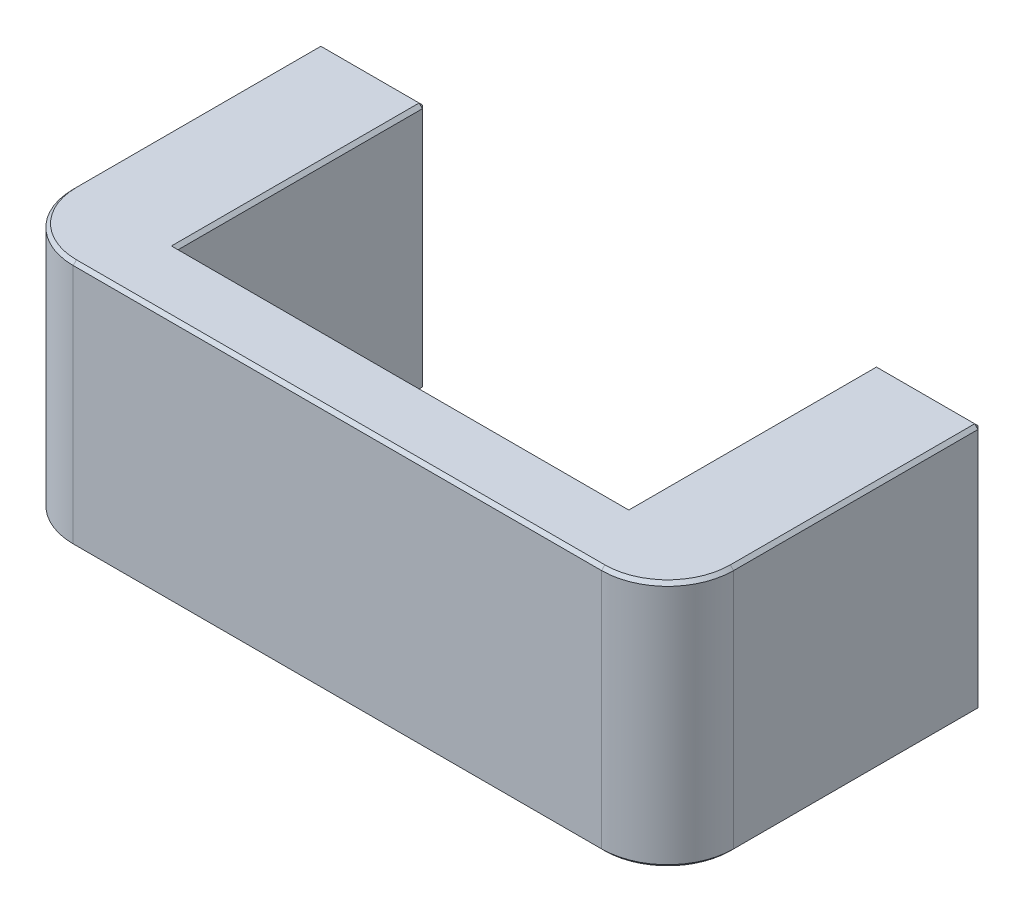
SolidWorks part; units mm, degrees
ref_plane "Front" through (0, 0, 0) normal (0, 0, 1) x (1, 0, 0)
ref_plane "Top" through (0, 0, 0) normal (0, 1, 0) x (1, 0, 0)
ref_plane "Right" through (0, 0, 0) normal (1, 0, 0) x (0, 0, -1)
ref_axis "Z AXIS" through (0, 0, 10.1914) along (0, 0, -1)
ref_axis "Y AXIS" through (0, 16.6631, 0) along (0, -1, 0)
ref_axis "X AXIS" through (18.31, 0, 0) along (-1, 0, 0)
sketch "Sketch1" plane through (0, 0, 0) normal (0, 1, 0) x (1, 0, 0)
  line L0 (-40, 30) -> (-40, -8)
  line L1 (-40, -8) -> (40, -8)
  line L2 (40, -8) -> (40, 30)
  line L3 (40, 30) -> (27.3, 30)
  line L4 (27.3, 30) -> (27.3, 0)
  line L5 (27.3, 0) -> (-27.3, 0)
  line L6 (-27.3, 0) -> (-27.3, 30)
  line L7 (-27.3, 30) -> (-40, 30)
  line L8 (-27.3, 30) -> (27.3, 30) construction
  line L9 (0, 30) -> (0, 0) construction
  point P10 (29.933, -21.2718)
  point P11 (18.5695, -1.5244)
  point P12 (0, 0)
  dimension "D1" = 54.6
  dimension "D2" = 30
  dimension "D3" = 8
  dimension "D4" = 80
extrude "Boss-Extrude1" add sketch "Sketch1" along normal blind 30
hole_wizard "Ø2.5mm Dowel Hole1" positions "Sketch4" profile "Sketch6" hole size "Ø2.5" standard "ISO"
sketch "Sketch4" plane through (0, 0, -30) normal (0, 0, -1) x (-1, 0, 0)
  line L4 (-40, 15) -> (40, 15) construction
  line L5 (-40, 30) -> (-40, 0) construction
  line L6 (40, 30) -> (40, 0) construction
  line L8 (0, 30) -> (0, 0) construction
  line L9 (-27.3, 30) -> (27.3, 30) construction
  line L10 (-33.65, 30) -> (-33.65, 15) construction
  line L11 (-40, 30) -> (-27.3, 30) construction
  point P30 (-33.65, 22.5)
  point P33 (-33.65, 7.5)
  point P34 (0, 0)
  point P35 (33.65, 22.5)
  point P36 (33.65, 7.5)
sketch "Sketch6" plane through (-33.65, 7.5, -30) normal (1, 0, 0) x (0, 1, 0)
  line L0 (0, 0) -> (0, 21.4421)
  line L1 (0, 21.4421) -> (2.4, 20)
  line L2 (2.4, 20) -> (2.4, 0.5)
  line L3 (2.4, 0.5) -> (2.9, 0)
  line L5 (2.9, 0) -> (0, 0)
  line L6 (-2.4, 0.5) -> (-2.9, 0) construction
  line L10 (0, 21.4421) -> (-2.4, 20) construction
  line L11 (0, -6.35) -> (0, 107.95) construction
  dimension "Hole Dia." = 4.8
  dimension "Hole Depth" = 20
  dimension "Near C'Sink Dia." = 5.8
  dimension "Near C'Sink Angle" = 90
  dimension "Drill Angle" = 118
fillet "Fillet1" radius 8 2 edges at (-40, 15, 8) (40, 15, 8)
chamfer "Chamfer1" distance 0.4 angle 45 24 edges at (-33.65, 30, -30) (-27.3, 30, -15) (0, 30, 0) (27.3, 30, -15) (33.65, 30, -30) (40, 30, -15) (37.6569, 30, 5.6569) (0, 30, 8) (-37.6569, 30, 5.6569) (-40, 30, -15) (37.6569, 0, 5.6569) (40, 0, -15) (40, 15, -30) (33.65, 0, -30) (0, 0, 8) (-37.6569, 0, 5.6569) (-40, 0, -15) (-40, 15, -30) (-33.65, 0, -30) (-27.3, 15, -30) (-27.3, 0, -15) (0, 0, 0) (27.3, 0, -15) (27.3, 15, -30)
